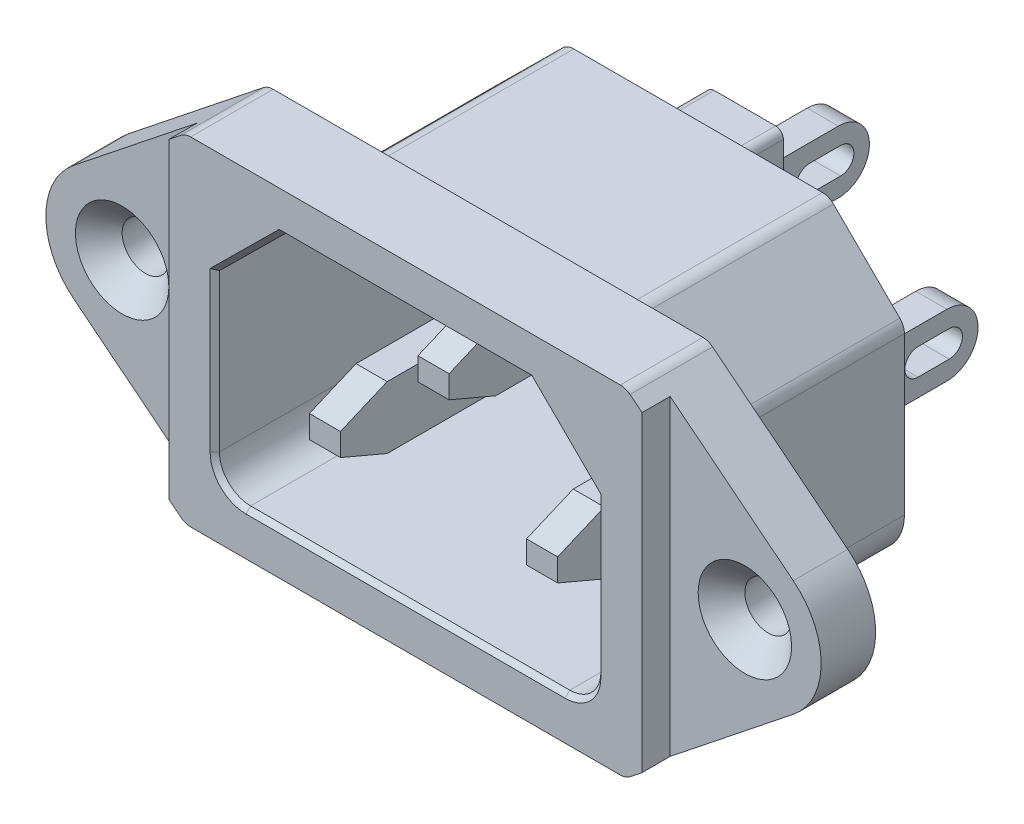
SolidWorks part; units mm, degrees
material "PVC Rigid"
ref_plane "Front Plane" through (0, 0, 0) normal (0, 0, 1) x (1, 0, 0)
ref_plane "Top Plane" through (0, 0, 0) normal (0, 1, 0) x (1, 0, 0)
ref_plane "Right Plane" through (0, 0, 0) normal (1, 0, 0) x (0, 0, -1)
sketch "Sketch1" plane through (0, 0, 0) normal (0, 0, 1) x (1, 0, 0)
  line L0 (1.791, 3.7158) -> (10.4766, 10.6323)
  line L1 (11.0995, 10.85) -> (38.7005, 10.85)
  line L2 (39.3234, 10.6323) -> (48.009, 3.7158)
  line L3 (48.009, -3.7158) -> (39.3234, -10.6323)
  line L4 (38.7005, -10.85) -> (11.0995, -10.85)
  line L5 (10.4766, -10.6323) -> (1.791, -3.7158)
  line L6 (4.75, 0) -> (45.05, 0) construction
  line L7 (24.9, 10.85) -> (24.9, -10.85) construction
  arc A0 (48.009, 3.7158) -> (48.009, -3.7158) centre (45.05, 0) cw
  arc A1 (1.791, 3.7158) -> (1.791, -3.7158) centre (4.75, 0) ccw
  arc A2 (11.0995, -10.85) -> (10.4766, -10.6323) centre (11.0995, -9.85) cw
  arc A3 (39.3234, -10.6323) -> (38.7005, -10.85) centre (38.7005, -9.85) cw
  arc A4 (38.7005, 10.85) -> (39.3234, 10.6323) centre (38.7005, 9.85) cw
  arc A5 (10.4766, 10.6323) -> (11.0995, 10.85) centre (11.0995, 9.85) cw
  circle A6 centre (4.9, 0) radius 1.5
  circle A7 centre (44.9, 0) radius 1.5
  point P12 (0, 0)
  point P13 (49.8, 0)
  point P21 (39.05, 10.85)
  point P24 (10.75, 10.85)
  dimension "D1" = 4.75
  dimension "D5" = 1
  dimension "D6" = 40
  dimension "D7" = 3
  dimension "D2" = 49.8
  dimension "D3" = 21.7
  dimension "D4" = 28.3
extrude "Boss-Extrude1" add sketch "Sketch1" along normal blind 21.8
sketch "Sketch2" plane through (0, 0, 21.8) normal (0, 0, 1) x (1, 0, 0)
  line L0 (11.0995, -10.85) -> (38.7005, -10.85) construction
  line L1 (11.0995, -10.85) -> (38.7005, -10.85)
  line L2 (9.7, -10.0139) -> (9.7, 10.0139)
  line L3 (11.0995, 10.85) -> (38.7005, 10.85)
  line L4 (40.1, -10.0139) -> (40.1, 10.0139)
  line L6 (24.9, -10.85) -> (24.9, -2.6264) construction
  line L7 (48.009, 3.7158) -> (39.3234, 10.6323) construction
  line L8 (39.3234, -10.6323) -> (48.009, -3.7158) construction
  line L9 (1.791, -3.7158) -> (10.4766, -10.6323) construction
  line L10 (10.4766, 10.6323) -> (1.791, 3.7158) construction
  line L11 (40.1, 10.0139) -> (39.3234, 10.6323)
  line L12 (39.3234, -10.6323) -> (40.1, -10.0139)
  line L13 (9.7, -10.0139) -> (10.4766, -10.6323)
  line L14 (10.4766, 10.6323) -> (9.7, 10.0139)
  line L16 (-4.1169, -19.3982) -> (50.7137, -19.3982)
  line L17 (-4.1169, -19.3982) -> (-4.1169, 12.7876)
  line L18 (-4.1169, 12.7876) -> (50.7137, 12.7876)
  line L19 (50.7137, -19.3982) -> (50.7137, 12.7876)
  arc A0 (39.3234, 10.6323) -> (38.7005, 10.85) centre (38.7005, 9.85) ccw construction
  arc A1 (38.7005, -10.85) -> (39.3234, -10.6323) centre (38.7005, -9.85) ccw construction
  arc A2 (10.4766, -10.6323) -> (11.0995, -10.85) centre (11.0995, -9.85) ccw construction
  arc A3 (11.0995, 10.85) -> (10.4766, 10.6323) centre (11.0995, 9.85) ccw construction
  arc A4 (39.3234, 10.6323) -> (38.7005, 10.85) centre (38.7005, 9.85) ccw
  arc A5 (38.7005, -10.85) -> (39.3234, -10.6323) centre (38.7005, -9.85) ccw
  arc A6 (10.4766, -10.6323) -> (11.0995, -10.85) centre (11.0995, -9.85) ccw
  arc A7 (11.0995, 10.85) -> (10.4766, 10.6323) centre (11.0995, 9.85) ccw
extrude "Cut-Extrude1" cut sketch "Sketch2" against normal blind 1.8
sketch "Sketch3" plane through (0, 0, 0) normal (0, 0, -1) x (-1, 0, 0)
  line L0 (-38.15, -9.05) -> (-38.15, 4.45)
  line L1 (-38.15, 4.45) -> (-33.3, 9.25)
  line L2 (-33.3, 9.25) -> (-16.5, 9.25)
  line L3 (-16.5, 9.25) -> (-11.65, 4.45)
  line L4 (-11.65, 4.45) -> (-11.65, -9.05)
  line L5 (-11.65, -9.05) -> (-38.15, -9.05)
  line L6 (-11.0995, -10.85) -> (-38.7005, -10.85) construction
  line L7 (-24.9, 9.25) -> (-24.9, -9.05) construction
  line L9 (-53.6764, -18.0994) -> (4.0477, -18.0994)
  line L10 (-53.6764, -18.0994) -> (-53.6764, 14.6166)
  line L11 (-53.6764, 14.6166) -> (4.0477, 14.6166)
  line L12 (4.0477, -18.0994) -> (4.0477, 14.6166)
  point P2 (-24.9, -10.85)
  point P7 (-24.9, -9.05)
  dimension "D1" = 26.5
  dimension "D2" = 18.3
  dimension "D3" = 1.8
  dimension "D4" = 16.8
  dimension "D5" = 13.5
extrude "Cut-Extrude2" cut sketch "Sketch3" against normal blind 16.5
fillet "Fillet1" radius 3 2 edges at (11.65, -9.05, 8.25) (38.15, -9.05, 8.25)
fillet "Fillet2" radius 1 4 edges at (38.15, 4.45, 8.25) (33.3, 9.25, 8.25) (16.5, 9.25, 8.25) (11.65, 4.45, 8.25)
sketch "Sketch4" plane through (0, 0, 21.8) normal (0, 0, 1) x (1, 0, 0)
  line L12 (37.15, 4.0327) -> (32.8888, 8.25)
  line L13 (37.15, -6.05) -> (37.15, 4.0327)
  line L14 (14.65, -8.05) -> (35.15, -8.05)
  line L15 (12.65, 4.0327) -> (12.65, -6.05)
  line L16 (16.9112, 8.25) -> (12.65, 4.0327)
  line L17 (32.8888, 8.25) -> (16.9112, 8.25)
  line L18 (37.15, 4.0327) -> (32.8888, 8.25)
  line L19 (37.15, -6.05) -> (37.15, 4.0327)
  line L20 (14.65, -8.05) -> (35.15, -8.05)
  line L21 (12.65, 4.0327) -> (12.65, -6.05)
  line L22 (16.9112, 8.25) -> (12.65, 4.0327)
  line L23 (32.8888, 8.25) -> (16.9112, 8.25)
  arc A12 (35.15, -8.05) -> (37.15, -6.05) centre (35.15, -6.05) ccw
  arc A13 (12.65, -6.05) -> (14.65, -8.05) centre (14.65, -6.05) ccw
  arc A14 (35.15, -8.05) -> (37.15, -6.05) centre (35.15, -6.05) ccw
  arc A15 (12.65, -6.05) -> (14.65, -8.05) centre (14.65, -6.05) ccw
  dimension "D1" = 1
extrude "Cut-Extrude3" cut sketch "Sketch4" against normal blind 17.8
chamfer "Chamfer1" distance 0.3 angle 45 8 edges at (37.15, -1.0086, 21.8) (36.5642, -7.4642, 21.8) (24.9, -8.05, 21.8) (13.2358, -7.4642, 21.8) (35.0194, 6.1414, 21.8) (12.65, -1.0086, 21.8) (14.7806, 6.1414, 21.8) (24.9, 8.25, 21.8)
chamfer "Chamfer2" distance 1.5 angle 45 2 edges at (3.4, 0, 20) (43.4, 0, 20)
sketch "Sketch5" plane through (0, 0, 0) normal (0, 0, -1) x (-1, 0, 0)
  line L1 (-26.875, -1.55) -> (-22.925, -1.55)
  line L2 (-27.375, -1.05) -> (-27.375, 7.95)
  line L3 (-26.875, 8.45) -> (-22.925, 8.45)
  line L4 (-22.425, -1.05) -> (-22.425, 7.95)
  line L5 (-19.9, -8.25) -> (-15.95, -8.25)
  line L6 (-20.4, -7.75) -> (-20.4, 1.25)
  line L7 (-19.9, 1.75) -> (-15.95, 1.75)
  line L8 (-15.45, -7.75) -> (-15.45, 1.25)
  line L9 (-33.85, -8.25) -> (-29.9, -8.25)
  line L10 (-34.35, -7.75) -> (-34.35, 1.25)
  line L11 (-33.85, 1.75) -> (-29.9, 1.75)
  line L12 (-29.4, -7.75) -> (-29.4, 1.25)
  line L14 (-35.15, -9.05) -> (-14.65, -9.05) construction
  line L15 (-16.9112, 9.25) -> (-32.8888, 9.25) construction
  line L16 (-40.7756, -11.3531) -> (-7.6971, -11.3531)
  line L17 (-40.7756, -11.3531) -> (-40.7756, 11.239)
  line L18 (-40.7756, 11.239) -> (-7.6971, 11.239)
  line L19 (-7.6971, -11.3531) -> (-7.6971, 11.239)
  arc A0 (-29.9, -8.25) -> (-29.4, -7.75) centre (-29.9, -7.75) ccw
  arc A1 (-34.35, 1.25) -> (-33.85, 1.75) centre (-33.85, 1.25) cw
  arc A2 (-29.9, 1.75) -> (-29.4, 1.25) centre (-29.9, 1.25) cw
  arc A3 (-33.85, -8.25) -> (-34.35, -7.75) centre (-33.85, -7.75) cw
  arc A4 (-15.95, -8.25) -> (-15.45, -7.75) centre (-15.95, -7.75) ccw
  arc A5 (-20.4, 1.25) -> (-19.9, 1.75) centre (-19.9, 1.25) cw
  arc A6 (-15.95, 1.75) -> (-15.45, 1.25) centre (-15.95, 1.25) cw
  arc A7 (-19.9, -8.25) -> (-20.4, -7.75) centre (-19.9, -7.75) cw
  arc A8 (-22.925, -1.55) -> (-22.425, -1.05) centre (-22.925, -1.05) ccw
  arc A9 (-27.375, 7.95) -> (-26.875, 8.45) centre (-26.875, 7.95) cw
  arc A10 (-22.925, 8.45) -> (-22.425, 7.95) centre (-22.925, 7.95) cw
  arc A11 (-26.875, -1.55) -> (-27.375, -1.05) centre (-26.875, -1.05) cw
  point P36 (-22.425, -1.55)
  point P39 (-27.375, 8.45)
  point P42 (-22.425, 8.45)
  dimension "D6" = 0.5
  dimension "D1" = 10
  dimension "D2" = 4.95
  dimension "D3" = 0.8
  dimension "D4" = 0.8
  dimension "D5" = 9
extrude "Cut-Extrude4" cut sketch "Sketch5" against normal blind 3
sketch "Sketch6" plane through (0, 0, 20) normal (0, 0, 1) x (1, 0, 0)
  line L1 (23.9, 1.45) -> (25.9, 1.45)
  line L2 (23.9, 1.45) -> (23.9, 5.45)
  line L3 (23.9, 5.45) -> (25.9, 5.45)
  line L4 (25.9, 1.45) -> (25.9, 5.45)
  line L5 (16.925, -5.25) -> (18.925, -5.25)
  line L6 (16.925, -5.25) -> (16.925, -1.25)
  line L7 (16.925, -1.25) -> (18.925, -1.25)
  line L8 (18.925, -5.25) -> (18.925, -1.25)
  line L9 (30.875, -5.25) -> (32.875, -5.25)
  line L10 (30.875, -5.25) -> (30.875, -1.25)
  line L11 (30.875, -1.25) -> (32.875, -1.25)
  line L12 (32.875, -5.25) -> (32.875, -1.25)
  line L13 (27.375, 7.95) -> (27.375, -1.05) construction
  line L14 (26.875, -1.55) -> (22.925, -1.55) construction
  line L15 (20.4, 1.25) -> (20.4, -7.75) construction
  line L16 (15.95, 1.75) -> (19.9, 1.75) construction
  line L17 (29.9, 1.75) -> (33.85, 1.75) construction
  line L18 (34.35, 1.25) -> (34.35, -7.75) construction
  point P12 (24.9, 1.45)
  point P13 (25.9, 3.45)
  point P14 (27.375, 3.45)
  point P15 (24.9, -1.55)
  point P18 (20.4, -3.25)
  point P21 (17.925, 1.75)
  point P22 (18.925, -3.25)
  point P25 (31.875, 1.75)
  point P28 (34.35, -3.25)
  point P31 (32.875, -3.25)
  point P34 (31.875, -1.25)
  point P36 (17.925, -1.25)
  dimension "D1" = 4
  dimension "D2" = 2
extrude "Boss-Extrude2" add sketch "Sketch6" against normal blind 27
chamfer "Chamfer3" distance 3 angle 23 6 edges at (31.875, -5.25, 20) (31.875, -1.25, 20) (17.925, -5.25, 20) (17.925, -1.25, 20) (24.9, 1.45, 20) (24.9, 5.45, 20) first distance on face at (31.875, -5.25, 12) first distance on face at (31.875, -1.25, 12) first distance on face at (17.925, -5.25, 12) first distance on face at (17.925, -1.25, 12) first distance on face at (24.9, 1.45, 12) first distance on face at (24.9, 5.45, 12)
sketch "Sketch7" plane through (25.9, 0, 0) normal (1, 0, 0) x (0, 0, -1)
  line L0 (3.15, 3.45) -> (5.15, 3.45) construction
  line L1 (3.15, 4.3) -> (5.15, 4.3)
  line L2 (3.15, 2.6) -> (5.15, 2.6)
  line L3 (3.15, -3.25) -> (5.15, -3.25) construction
  line L4 (3.15, -2.4) -> (5.15, -2.4)
  line L5 (3.15, -4.1) -> (5.15, -4.1)
  line L6 (7, 1.45) -> (7, 5.45) construction
  line L7 (7, -5.25) -> (7, -1.25) construction
  arc A0 (3.15, 4.3) -> (3.15, 2.6) centre (3.15, 3.45) ccw
  arc A1 (5.15, 2.6) -> (5.15, 4.3) centre (5.15, 3.45) ccw
  arc A2 (3.15, -2.4) -> (3.15, -4.1) centre (3.15, -3.25) ccw
  arc A3 (5.15, -4.1) -> (5.15, -2.4) centre (5.15, -3.25) ccw
  point P2 (4.15, 3.45)
  point P7 (4.15, -3.25)
  point P14 (7, -3.25)
  point P15 (7, 3.45)
  point P16 (6, -3.25)
  point P21 (6, 3.45)
  dimension "D1" = 0.85
  dimension "D2" = 1
  dimension "D3" = 2
extrude "Cut-Extrude5" cut sketch "Sketch7" against normal through all both and the other way through all
fillet "Fillet3" radius 2 6 edges at (31.875, -5.25, -7) (31.875, -1.25, -7) (17.925, -5.25, -7) (24.9, 1.45, -7) (17.925, -1.25, -7) (24.9, 5.45, -7)
